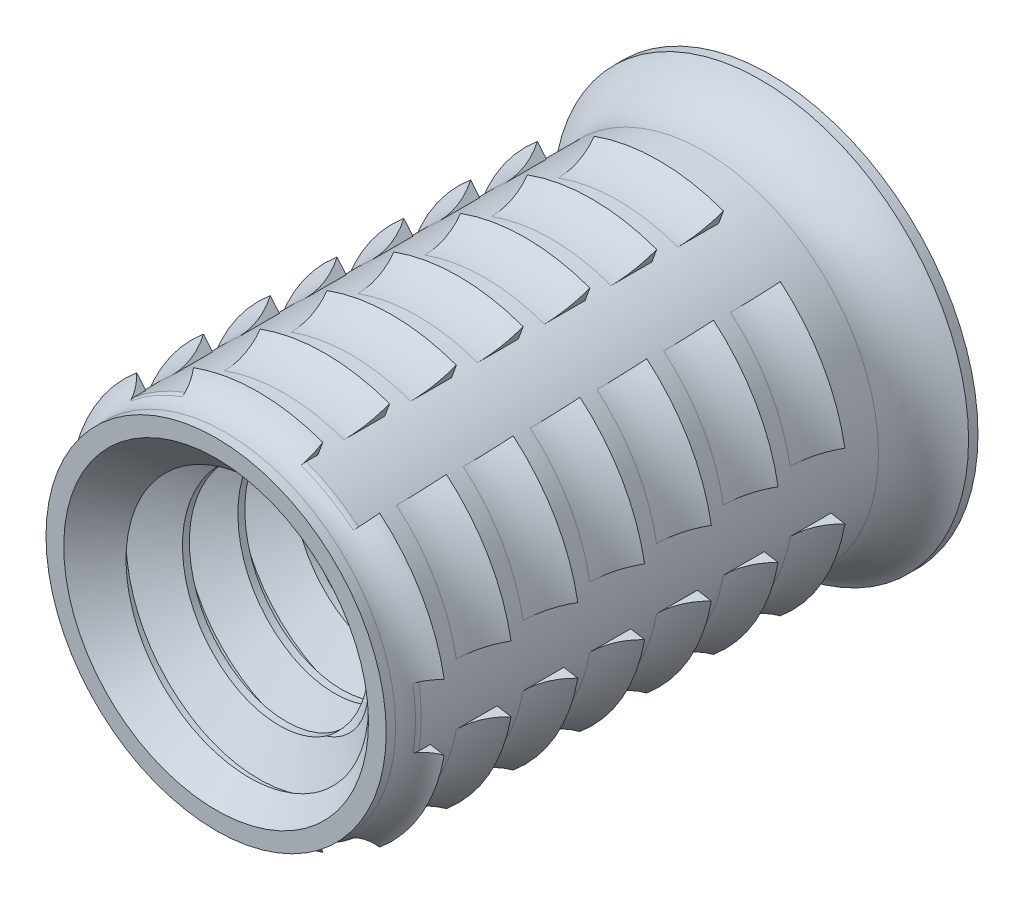
SolidWorks part; units mm, degrees
material "Brass"
ref_plane "Front" through (0, 0, 0) normal (0, 0, 1) x (1, 0, 0)
ref_plane "Top" through (0, 0, 0) normal (0, 1, 0) x (1, 0, 0)
ref_plane "Right" through (0, 0, 0) normal (1, 0, 0) x (0, 0, -1)
sketch "Sketch1" plane through (0, 0, 0) normal (1, 0, 0) x (0, 0, -1)
  line L0 (-6.35, 0) -> (6.35, 0) construction
  line L1 (-6.35, 3.175) -> (6.35, 3.175)
  line L2 (6.35, 3.175) -> (6.35, 4.7625)
  line L3 (-6.35, 3.175) -> (-6.35, 4.7625)
  line L4 (-6.35, 3.8989) -> (6.35, 3.8989) construction
  line L5 (-6.35, 4.7625) -> (6.35, 4.7625)
  line L6 (-6.35, 4.3307) -> (6.35, 4.3307) construction
revolve "Revolve1" add sketch "Sketch1" angle 360 about L0
sketch "Sketch2" plane through (0, 0, 0) normal (1, 0, 0) x (0, 0, -1)
  line L0 (-6.35, 0) -> (6.35, 0) construction
  line L1 (-6.35, 4.7625) -> (-6.35, -4.7625) construction
  line L2 (-6.35, 4.3307) -> (6.35, 4.3307) construction
  line L3 (-6.35, 3.8989) -> (6.35, 3.8989) construction
  line L4 (-6.35, 3.8989) -> (-6.35, 4.7625)
  line L5 (-6.35, 4.7625) -> (6.1341, 4.7625)
  line L8 (-6.1341, 3.8989) -> (-6.35, 3.8989)
  line L10 (-6.1341, 3.8989) -> (-6.1341, 4.3307) construction
  line L11 (-6.1341, 4.3307) -> (-6.1341, 4.7625) construction
  line L12 (0, 4.7625) -> (0, 4.5466) construction
  line L13 (6.35, 4.7625) -> (-6.35, 4.7625) construction
  line L14 (0, 4.5466) -> (0, 4.3307) construction
  line L15 (0, 4.3307) -> (0, 4.2227) construction
  line L16 (0, 4.2227) -> (0, 4.1148) construction
  line L17 (0, 4.1148) -> (0, 4.0068) construction
  line L18 (0, 4.0068) -> (0, 3.8989) construction
  line L19 (-6.35, 3.8989) -> (6.35, 3.8989) construction
  line L20 (0, 4.0068) -> (1.7424, 4.0068) construction
  line L22 (4.8253, 5.5181) -> (4.8253, 4.7625) construction
  line L23 (4.8253, 4.7625) -> (4.8253, 4.0069) construction
  line L24 (4.8253, 4.0069) -> (4.7173, 4.0069)
  line L25 (6.35, 4.7625) -> (6.1341, 4.7625) construction
  line L26 (4.7173, 4.3307) -> (4.7173, 4.0069)
  line L28 (-5.3862, 4.3307) -> (4.7173, 4.3307)
  arc A0 (-6.1341, 3.8989) -> (-5.3862, 4.3307) centre (-6.1341, 4.7625) ccw
  arc A1 (4.8253, 4.0069) -> (6.1341, 4.7625) centre (4.8253, 5.5181) ccw
  dimension "D1" = 1.6327
  dimension "D2" = 0.9638
revolve "Cut-Revolve1" cut sketch "Sketch2" angle 360 about L0
sketch "Sketch3" plane through (0, 0, 0) normal (1, 0, 0) x (0, 0, -1)
  line L0 (-5.3862, 4.3307) -> (-5.3862, 4.0069)
  line L1 (-5.3862, 4.3307) -> (-5.3862, -4.3307) construction
  line L2 (-5.3862, 4.0069) -> (-4.7904, 4.0069)
  line L4 (0, 4.0068) -> (1.7424, 4.0068) construction
  line L5 (4.8253, 4.0069) -> (4.7173, 4.0069) construction
  line L6 (-3.8556, 4.3307) -> (-5.3862, 4.3307)
  line L7 (-6.35, 4.3307) -> (6.35, 4.3307) construction
  line L8 (-4.7904, 5.5181) -> (-4.7904, 4.7625) construction
  line L9 (-6.35, 4.7625) -> (6.35, 4.7625) construction
  line L10 (-4.7904, 4.7625) -> (-4.7904, 4.0069) construction
  line L11 (-6.35, 0) -> (6.35, 0) construction
  arc A0 (-4.7904, 4.0069) -> (-3.8556, 4.3307) centre (-4.7904, 5.5181) ccw
  dimension "D1" = 1.5306
revolve "Cut-Revolve2" cut sketch "Sketch3" angle 360 about L11
pattern_linear "LPattern1" count 6 spacing 1.5306 along (0, 0, -1) of "Cut-Revolve2"
sketch "Sketch4" plane through (0, 0, -4.7173) normal (0, 0, -1) x (-1, 0, 0)
  circle A0 centre (0, 0) radius 4.0069 construction
  circle A1 centre (0, 0) radius 4.3307 construction
  circle A2 centre (0, 0) radius 4.0068
  circle A3 centre (0, 0) radius 4.3307
extrude "Cut-Extrude1" cut sketch "Sketch4" against normal blind 0.9197
sketch "Sketch5" plane through (0, 0, 6.35) normal (0, 0, 1) x (1, 0, 0)
  line L0 (3.946, 0.6958) -> (4.6901, 0.827)
  line L1 (3.946, -0.6958) -> (4.6901, -0.827)
  line L2 (0, 0) -> (4.7625, 0) construction
  line L3 (2.5756, -3.0694) -> (3.0613, -3.6483)
  line L4 (1.3704, -3.7652) -> (1.6289, -4.4753)
  line L5 (-1.3704, -3.7652) -> (-1.6289, -4.4753)
  line L6 (-2.5756, -3.0694) -> (-3.0613, -3.6483)
  line L7 (-3.946, -0.6958) -> (-4.6901, -0.827)
  line L8 (-3.946, 0.6958) -> (-4.6901, 0.827)
  line L9 (-2.5756, 3.0694) -> (-3.0613, 3.6483)
  line L10 (-1.3704, 3.7652) -> (-1.6289, 4.4753)
  line L11 (1.3704, 3.7652) -> (1.6289, 4.4753)
  line L12 (2.5756, 3.0694) -> (3.0613, 3.6483)
  circle A0 centre (0, 0) radius 4.0069 construction
  arc A1 (3.946, -0.6958) -> (3.946, 0.6958) centre (0, 0) ccw
  circle A2 centre (0, 0) radius 4.7625 construction
  arc A3 (4.6901, -0.827) -> (4.6901, 0.827) centre (0, 0) ccw
  circle A4 centre (0, 0) radius 4.7625 construction
  arc A5 (1.3704, -3.7652) -> (2.5756, -3.0694) centre (0, 0) ccw
  arc A6 (1.6289, -4.4753) -> (3.0613, -3.6483) centre (0, 0) ccw
  arc A7 (-2.5756, -3.0694) -> (-1.3704, -3.7652) centre (0, 0) ccw
  arc A8 (-3.0613, -3.6483) -> (-1.6289, -4.4753) centre (0, 0) ccw
  arc A9 (-3.946, 0.6958) -> (-3.946, -0.6958) centre (0, 0) ccw
  arc A10 (-4.6901, 0.827) -> (-4.6901, -0.827) centre (0, 0) ccw
  arc A11 (-1.3704, 3.7652) -> (-2.5756, 3.0694) centre (0, 0) ccw
  arc A12 (-1.6289, 4.4753) -> (-3.0613, 3.6483) centre (0, 0) ccw
  arc A13 (2.5756, 3.0694) -> (1.3704, 3.7652) centre (0, 0) ccw
  arc A14 (3.0613, 3.6483) -> (1.6289, 4.4753) centre (0, 0) ccw
  point P32 (0, 0)
  dimension "D1" = 20
  dimension "D2" = 6
extrude "Cut-Extrude2" cut sketch "Sketch5" against normal up to surface (10.1476 mm away) up to face at (-4.0068, 0, -3.7976)
fillet "Fillet1" radius 0.254 6 edges at (-4.0069, 0, 5.716) (-2.0034, -3.47, 5.716) (2.0034, -3.47, 5.716) (4.0069, 0, 5.716) (2.0034, 3.47, 5.716) (-2.0034, 3.47, 5.716)
sketch "Sketch6" plane through (0, 0, 6.35) normal (0, 0, 1) x (1, 0, 0)
  circle A0 centre (0, 0) radius 3.175 construction
  circle A1 centre (0, 0) radius 3.175
curve "Helix/Spiral1" pitch 1.27 height 13.97 radius 3.175 centre (0, 0, 6.35) axis (0, 0, -1) start towards (0, 1, 0) parameters "Pitch"=1.27
sketch "Sketch7" plane through (0, 0, 0) normal (1, 0, 0) x (0, 0, -1)
  line L0 (-6.35, 3.175) -> (-6.8263, 2.3501)
  line L1 (-6.8263, 2.3501) -> (-6.985, 2.3501)
  line L2 (-6.985, 2.3501) -> (-7.4979, 3.2385)
  line L3 (-7.4979, 3.2385) -> (-6.3133, 3.2385)
  line L4 (-6.3133, 3.2385) -> (-6.35, 3.175)
  line L5 (-6.5881, 2.7626) -> (-7.2231, 2.7626) construction
  line L6 (-6.9056, 2.7626) -> (-6.9056, 2.3501) construction
  dimension "D1" = 0.0635
  dimension "D2" = 60
  dimension "D3" = 0.1588
  dimension "D4" = 0.635
sketch "Sketch8" plane through (0, 0, 0) normal (1, 0, 0) x (0, 0, -1)
  line L0 (-6.35, 3.175) -> (-6.35, 3.4925) construction
  line L1 (-6.9056, 2.3501) -> (-6.9056, 2.1914) construction
  line L2 (-6.35, 0) -> (6.35, 0) construction
  line L4 (-6.35, 3.8989) -> (-6.35, -3.8989) construction
  line L6 (6.35, -4.7625) -> (6.35, 4.7625) construction
  line L8 (-7.4979, 3.2385) -> (-8.6825, 3.2385) construction
  line L9 (0, 0) -> (0, 4.7625) construction
  line L10 (-6.35, 4.7625) -> (6.35, 4.7625) construction
  line L11 (-8.6825, 3.4925) -> (-6.35, 3.4925)
  line L12 (-8.6825, 0) -> (-8.6825, 3.4925)
  line L13 (-5.0489, 0) -> (-8.6825, 0)
  line L14 (-6.35, 3.4925) -> (-5.0489, 2.1914)
  line L15 (-6.9056, 2.1914) -> (-5.0489, 2.1914) construction
  line L16 (-6.8263, 2.3501) -> (-6.985, 2.3501) construction
  line L17 (-5.0489, 2.1914) -> (-5.0489, 0)
  line L18 (-7.4979, 3.2385) -> (-6.3133, 3.2385) construction
  line L19 (8.6825, 0) -> (8.6825, 3.4925)
  line L20 (8.6825, 3.4925) -> (6.35, 3.4925)
  line L21 (6.35, 3.4925) -> (5.0489, 2.1914)
  line L22 (5.0489, 0) -> (8.6825, 0)
  line L23 (5.0489, 2.1914) -> (5.0489, 0)
  dimension "D1" = 0.3175
  dimension "D2" = 45
sketch "Sketch9" plane through (0, 0, -6.35) normal (0, 0, -1) x (-1, 0, 0)
  line L0 (0, 4.7625) -> (0, -4.7625) construction
  line L1 (-4.7625, 0) -> (4.7625, 0) construction
  circle A0 centre (0, 0) radius 4.7625 construction
sweep "Sweep1" add profiles "Sketch7" path "Helix/Spiral1"
revolve "Cut-Revolve3" cut sketch "Sketch8" angle 360 about L13
ref_plane "Contact Plane 1" through (0, 4.7625, 0) normal (0, 1, 0) x (1, 0, 0)
ref_plane "Contact Plane 2" through (0, -4.7625, 0) normal (0, 1, 0) x (1, 0, 0)
ref_plane "Contact Plane 3" through (4.7625, 0, 0) normal (1, 0, 0) x (0, 0, -1)
ref_plane "Contact Plane 4" through (-4.7625, 0, 0) normal (1, 0, 0) x (0, 0, -1)
ref_plane "Contact Plane 5" through (0, 0, -6.35) normal (0, 0, -1) x (-1, 0, 0)
ref_plane "Contact Plane 6" through (0, 0, 6.35) normal (0, 0, 1) x (1, 0, 0)
equation "\"D1@Sketch3\"=\"D1@Sketch2\"*.9375"
equation "\"D1@Cut-Extrude1\"=\"InstalledLength@Sketch1\"-\"D2@Sketch2\"-\"D1@Sketch2\"-(\"D1@Sketch3\"*\"D1@LPattern1\")"
equation "\"D3@Helix/Spiral1\"=\"InstalledLength@Sketch1\"+\"Pitch@Helix/Spiral1\""
equation "\"D3@Sketch7\"=\"Pitch@Helix/Spiral1\"*.125"
equation "\"D4@Sketch7\"=\"Pitch@Helix/Spiral1\"*.5"
equation "\"D1@Sketch8\"=\"Pitch@Helix/Spiral1\"*.25"
equation "\"D3@LPattern1\"=\"D1@Sketch3\""
equation "\"D1@LPattern1\"=(INT((\"InstalledLength@Sketch1\"-\"D2@Sketch2\"-\"D1@Sketch2\"-\"D1@Sketch3\")/\"D1@Sketch3\"))+1"
